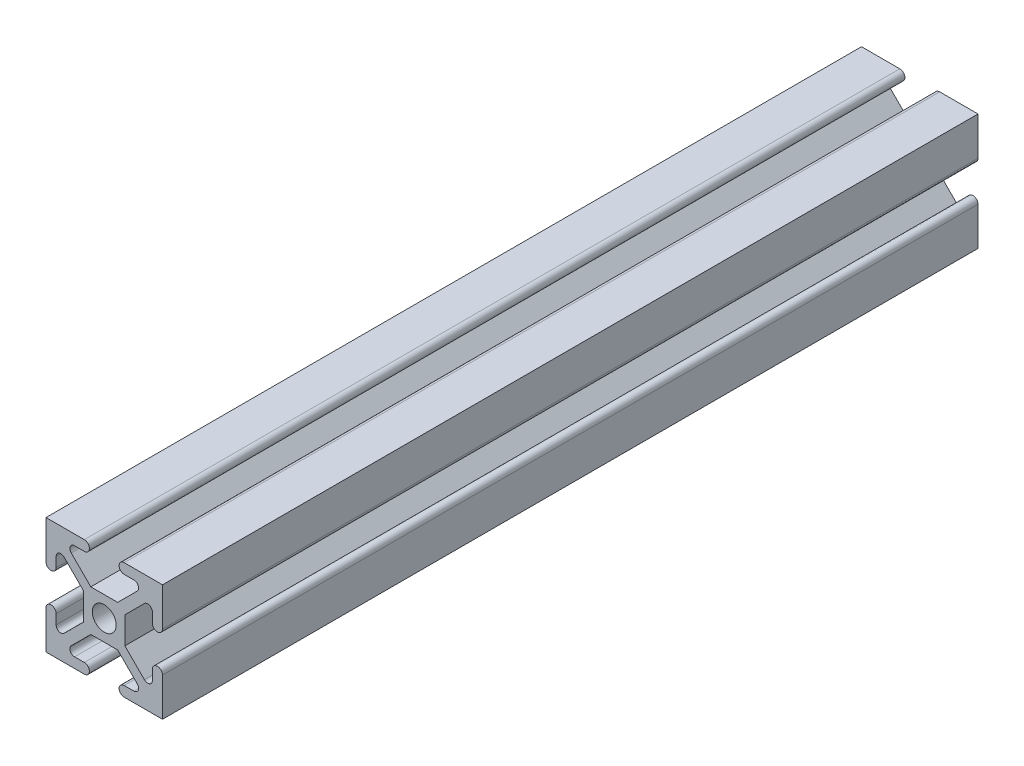
SolidWorks part; units mm, degrees
ref_plane "Front Plane" through (0, 0, 0) normal (0, 0, 1) x (1, 0, 0)
ref_plane "Top Plane" through (0, 0, 0) normal (0, 1, 0) x (1, 0, 0)
ref_plane "Right Plane" through (0, 0, 0) normal (1, 0, 0) x (0, 0, -1)
sketch "Sketch1" plane through (0, 0, 0) normal (0, 0, 1) x (1, 0, 0)
  line L2 (-12.7, -12.7) -> (-4.3434, -12.7)
  line L3 (-4.3434, -10.4902) -> (-6.4748, -10.4902)
  line L4 (-7.1932, -8.7558) -> (-2.9332, -4.4958)
  line L5 (-2.9332, -4.4958) -> (2.9332, -4.4958)
  line L6 (2.9332, -4.4958) -> (7.1932, -8.7558)
  line L7 (6.4748, -10.4902) -> (4.3434, -10.4902)
  line L8 (4.3434, -12.7) -> (12.7, -12.7)
  line L11 (12.7, -12.7) -> (12.7, -4.3434)
  line L12 (10.4902, -4.3434) -> (10.4902, -6.4748)
  line L13 (8.7558, -7.1932) -> (4.4958, -2.9332)
  line L14 (4.4958, -2.9332) -> (4.4958, 2.9332)
  line L15 (4.4958, 2.9332) -> (8.7558, 7.1932)
  line L16 (10.4902, 6.4748) -> (10.4902, 4.3434)
  line L17 (12.7, 4.3434) -> (12.7, 12.7)
  line L20 (12.7, 12.7) -> (4.3434, 12.7)
  line L21 (4.3434, 10.4902) -> (6.4748, 10.4902)
  line L22 (7.1932, 8.7558) -> (2.9332, 4.4958)
  line L23 (2.9332, 4.4958) -> (-2.9332, 4.4958)
  line L24 (-2.9332, 4.4958) -> (-7.1932, 8.7558)
  line L25 (-6.4748, 10.4902) -> (-4.3434, 10.4902)
  line L26 (-4.3434, 12.7) -> (-12.7, 12.7)
  line L29 (-12.7, 12.7) -> (-12.7, 4.3434)
  line L30 (-10.4902, 4.3434) -> (-10.4902, 6.4748)
  line L31 (-8.7558, 7.1932) -> (-4.4958, 2.9332)
  line L32 (-4.4958, 2.9332) -> (-4.4958, -2.9332)
  line L33 (-4.4958, -2.9332) -> (-8.7558, -7.1932)
  line L34 (-10.4902, -6.4748) -> (-10.4902, -4.3434)
  line L35 (-12.7, -4.3434) -> (-12.7, -12.7)
  circle A0 centre (0, 0) radius 2.6035
  arc A6 (-4.3434, -12.7) -> (-4.3434, -10.4902) centre (-4.3434, -11.5951) ccw
  arc A7 (-6.4748, -10.4902) -> (-7.1932, -8.7558) centre (-6.4748, -9.4742) cw
  arc A10 (7.1932, -8.7558) -> (6.4748, -10.4902) centre (6.4748, -9.4742) cw
  arc A11 (4.3434, -10.4902) -> (4.3434, -12.7) centre (4.3434, -11.5951) ccw
  arc A17 (12.7, -4.3434) -> (10.4902, -4.3434) centre (11.5951, -4.3434) ccw
  arc A18 (10.4902, -6.4748) -> (8.7558, -7.1932) centre (9.4742, -6.4748) cw
  arc A21 (8.7558, 7.1932) -> (10.4902, 6.4748) centre (9.4742, 6.4748) cw
  arc A22 (10.4902, 4.3434) -> (12.7, 4.3434) centre (11.5951, 4.3434) ccw
  arc A28 (4.3434, 12.7) -> (4.3434, 10.4902) centre (4.3434, 11.5951) ccw
  arc A29 (6.4748, 10.4902) -> (7.1932, 8.7558) centre (6.4748, 9.4742) cw
  arc A32 (-7.1932, 8.7558) -> (-6.4748, 10.4902) centre (-6.4748, 9.4742) cw
  arc A33 (-4.3434, 10.4902) -> (-4.3434, 12.7) centre (-4.3434, 11.5951) ccw
  arc A39 (-12.7, 4.3434) -> (-10.4902, 4.3434) centre (-11.5951, 4.3434) ccw
  arc A40 (-10.4902, 6.4748) -> (-8.7558, 7.1932) centre (-9.4742, 6.4748) cw
  arc A43 (-8.7558, -7.1932) -> (-10.4902, -6.4748) centre (-9.4742, -6.4748) cw
  arc A44 (-10.4902, -4.3434) -> (-12.7, -4.3434) centre (-11.5951, -4.3434) ccw
  point P101 (-4.4958, 0)
  point P102 (0, 4.4958)
  point P103 (4.4958, 0)
  point P127 (0, -4.4958)
extrude "Boss-Extrude1" add sketch "Sketch1" against normal blind 177.8
